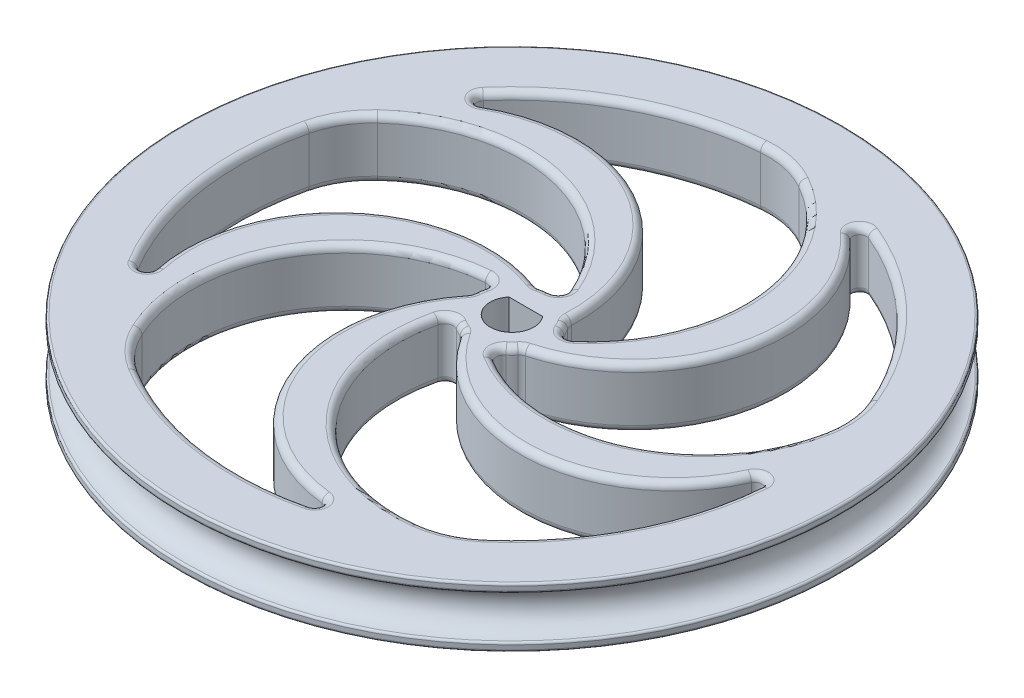
SolidWorks part; units mm, degrees
ref_plane "Front Plane" through (0, 0, 0) normal (0, 0, 1) x (1, 0, 0)
ref_plane "Top Plane" through (0, 0, 0) normal (0, 1, 0) x (1, 0, 0)
ref_plane "Right Plane" through (0, 0, 0) normal (1, 0, 0) x (0, 0, -1)
sketch "Sketch1" plane through (0, 0, 0) normal (0, 0, 1) x (1, 0, 0)
  line L0 (24.5875, 4.445) -> (24.5875, 3.81)
  line L1 (0, 0) -> (24.5875, 0)
  line L2 (0, 0) -> (0, 4.445)
  line L3 (0, 4.445) -> (24.5875, 4.445)
  line L5 (24.5875, 0.635) -> (24.5875, 0)
  arc A0 (24.5875, 3.81) -> (24.5875, 0.635) centre (24.5875, 2.2225) ccw
  dimension "D1" = 1.5875
  dimension "D4" = 180
  dimension "D2" = 4.445
  dimension "D3" = 23
revolve "rim revolve" add sketch "Sketch1" angle 360 about L2
fillet "lip bevel" radius 0.1588 4 edges at (0, 0, -24.5875) (0, 0.635, -24.5875) (0, 3.81, -24.5875) (0, 4.445, -24.5875)
sketch "Sketch3" plane through (0, 4.445, 0) normal (0, 1, 0) x (1, 0, 0)
  line L0 (0, 0) -> (0, 29.6275) construction
  line L1 (0, 0) -> (18.2335, 26.0401) construction
  line L2 (1.2287, -0.8604) -> (20.436, 26.5705) construction
  line L3 (2.4575, -1.7207) -> (20.4848, 24.025) construction
  circle A0 centre (0, 0) radius 20.32
  circle A1 centre (0, 0) radius 3
  arc A3 (0, 20.32) -> (1.2287, -0.8604) centre (-3.6668, 9.4815) cw
  arc A4 (2.4575, -1.7207) -> (4.2248, 19.876) centre (-0.3255, 9.3777) ccw
  arc A5 (19.3255, 6.2792) -> (-0.4386, -1.4345) centre (7.8843, 6.4173) cw
  arc A6 (-0.8771, -2.8689) -> (20.2087, 2.124) centre (8.8181, 3.2075) ccw
  arc A7 (11.9438, -16.4392) -> (-1.4998, -0.0262) centre (8.5396, -5.5154) cw
  arc A8 (-2.9995, -0.0524) -> (8.2649, -18.5632) centre (5.7754, -7.3953) ccw
  arc A9 (-11.9438, -16.4392) -> (-0.4884, 1.4183) centre (-2.6066, -9.8259) cw
  arc A10 (-0.9767, 2.8366) -> (-15.1007, -13.5967) centre (-5.2487, -7.778) ccw
  arc A11 (-19.3255, 6.2792) -> (1.198, 0.9027) centre (-10.1505, -0.5574) cw
  arc A12 (2.3959, 1.8054) -> (-17.5976, 10.16) centre (-9.0193, 2.5883) ccw
  circle A13 centre (0, 0) radius 1.5
  point P18 (2.9947, 0.1785)
  point P45 (0, 0)
  dimension "D1" = 35
  dimension "D2" = 6
  dimension "D3" = 40.64
  dimension "D4" = 12
  dimension "D6" = 3
  dimension "D5" = 5
extrude "spokes" cut sketch "Sketch3" against normal through all contours A12 A1 A3 A0 | A5 A0 A4 A1 | A7 A0 A6 A1 | A9 A0 A8 A1 | A11 A0 A10 A1 region at (7.9885, 4.445, 10.2111) region at (12.18, 4.445, -4.4421) region at (-7.2428, 4.445, 10.753) region at (-0.4609, 4.445, -12.9565) region at (-12.4648, 4.445, -3.5654)
fillet "hub fillet" radius 0.635 10 edges at (2.9947, 2.2225, -0.1785) (0.7556, 2.2225, -2.9033) (-0.9767, 2.2225, -2.8366) (-2.5277, 2.2225, -1.6158) (-2.9995, 2.2225, 0.0524) (-0.8771, 2.2225, 2.8689) (-2.3178, 2.2225, 1.9047) (1.0952, 2.2225, 2.7929) (2.4575, 2.2225, 1.7207) (2.3959, 2.2225, -1.8054)
fillet "spokes to rim obtuse fillet" radius 6.35 5 edges at (0, 2.2225, -20.32) (19.3255, 2.2225, -6.2792) (11.9438, 2.2225, 16.4392) (-11.9438, 2.2225, 16.4392) (-19.3255, 2.2225, -6.2792)
fillet "spokes to rim acute fillet" radius 0.508 5 edges at (-15.1007, 2.2225, 13.5967) (8.2649, 2.2225, 18.5632) (20.2087, 2.2225, -2.124) (4.2248, 2.2225, -19.876) (-17.5976, 2.2225, -10.16)
fillet "hub face fillet" radius 0.508 80 edges at (-16.7447, 4.445, 10.7582) (-12.7001, 4.445, -0.905) (-0.9824, 4.445, -2.8742) (-0.4726, 4.445, -2.9625) (0.35, 4.445, -3.2925) (-7.7196, 4.445, -10.6234) (-19.0866, 4.445, -6.3864) (-20.0673, 4.445, 3.1949) (19.8703, 4.445, 1.1388) (9.7426, 4.445, 8.1971) (-0.8946, 4.445, 2.9027) (-1.359, 4.445, 2.6745) (-2.2185, 4.445, 2.458) (0.001, 4.445, 13.132) (11.6876, 4.445, 16.3855) (18.1127, 4.445, 9.2105) (-15.406, 4.445, -12.6007) (-3.0638, 4.445, -12.3582) (2.4299, 4.445, -1.8225) (2.6715, 4.445, -1.3649) (3.2395, 4.445, -0.6846) (7.718, 4.445, -10.6246) (0.1757, 4.445, -20.1259) (-9.2397, 4.445, -18.0978) (7.2233, 4.445, -18.5458) (10.8066, 4.445, -6.7328) (2.4842, 4.445, 1.7478) (2.1237, 4.445, 2.119) (1.6521, 4.445, 2.8694) (12.4896, 4.445, 4.057) (19.1952, 4.445, -6.0522) (14.3568, 4.445, -14.38) (5.0572, 4.445, 19.2496) (-4.7853, 4.445, 11.7989) (-3.0371, 4.445, 0.0462) (-2.9636, 4.445, -0.466) (-3.0232, 4.445, -1.3503) (-12.4889, 4.445, 4.059) (-11.9719, 4.445, 16.179) (-3.1626, 4.445, 20.0724) (-0.9824, 0, -2.8742) (-12.7001, 0, -0.905) (-16.7447, 0, 10.7582) (-20.0673, 0, 3.1949) (-19.0866, 0, -6.3864) (-7.7196, 0, -10.6234) (0.35, 0, -3.2925) (-0.4726, 0, -2.9625) (-0.8946, 0, 2.9027) (9.7426, 0, 8.1971) (19.8703, 0, 1.1388) (18.1127, 0, 9.2105) (11.6876, 0, 16.3855) (0.001, 0, 13.132) (-2.2185, 0, 2.458) (-1.359, 0, 2.6745) (3.2395, 0, -0.6846) (2.6715, 0, -1.3649) (2.4299, 0, -1.8225) (-3.0638, 0, -12.3582) (-15.406, 0, -12.6007) (-9.2397, 0, -18.0978) (0.1757, 0, -20.1259) (7.718, 0, -10.6246) (2.4842, 0, 1.7478) (10.8066, 0, -6.7328) (7.2233, 0, -18.5458) (14.3568, 0, -14.38) (19.1952, 0, -6.0522) (12.4896, 0, 4.057) (1.6521, 0, 2.8694) (2.1237, 0, 2.119) (-3.0371, 0, 0.0462) (-4.7853, 0, 11.7989) (5.0572, 0, 19.2496) (-3.1626, 0, 20.0724) (-11.9719, 0, 16.179) (-12.4889, 0, 4.059) (-3.0232, 0, -1.3503) (-2.9636, 0, -0.466)
sketch "Sketch2" plane through (0, 4.445, 0) normal (0, 1, 0) x (1, 0, 0)
  line L0 (-1.261, 1.025) -> (1.261, 1.025)
  circle A0 centre (0, 0) radius 1.625
  dimension "D1" = 3.25
  dimension "D2" = 2.65
extrude "axle cut" cut sketch "Sketch2" against normal through all contours L0 A0 region at (0, 4.445, 0.1845)
ref_plane "Plane1" through (0, 2.2225, 0) normal (0, 1, 0) x (1, 0, 0)
